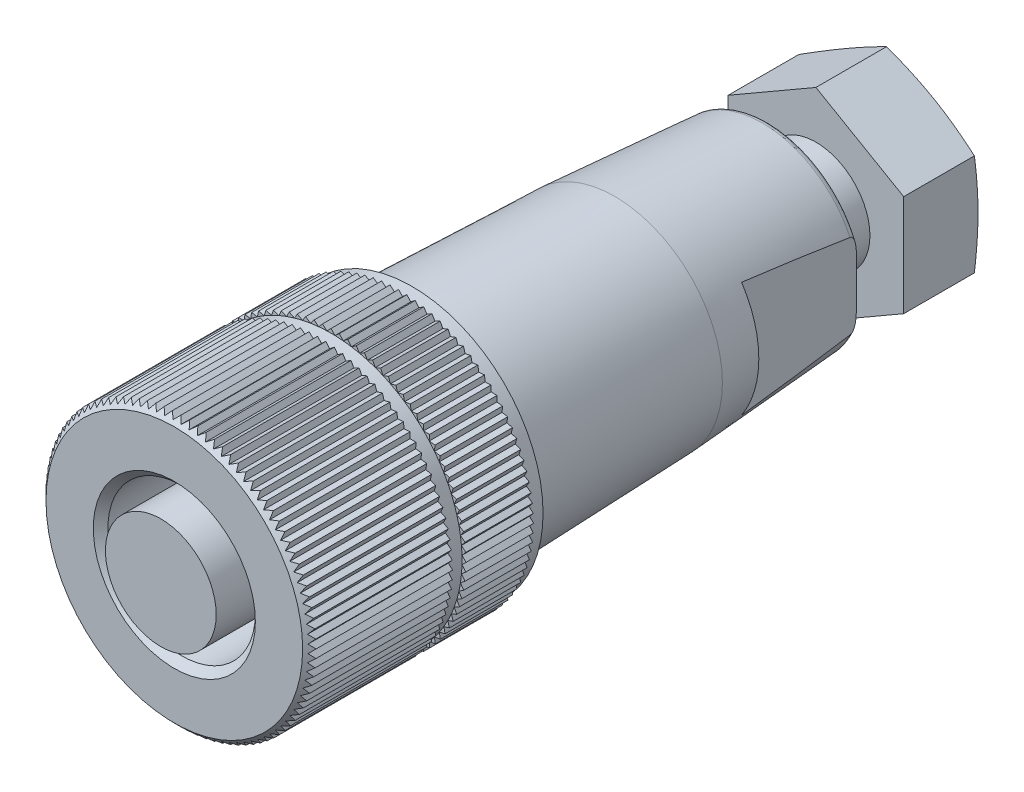
SolidWorks part; units mm, degrees
ref_plane "Ebene vorne" through (0, 0, 0) normal (0, 0, 1) x (1, 0, 0)
ref_plane "Ebene oben" through (0, 0, 0) normal (0, 1, 0) x (1, 0, 0)
ref_plane "Ebene rechts" through (0, 0, 0) normal (1, 0, 0) x (0, 0, -1)
ref_plane "Ebene1" through (0, 0, -26) normal (0, 0, 1) x (1, 0, 0)
sketch "Skizze1" plane through (0, 0, 0) normal (1, 0, 0) x (0, 0, -1)
  line L0 (0, 0) -> (0, 4.1)
  line L1 (0, 4.1) -> (1, 4.1)
  line L2 (1, 4.1) -> (1, 9.5)
  line L3 (1, 9.5) -> (1.5, 10)
  line L4 (1.5, 10) -> (11.6, 10)
  line L5 (11.6, 10) -> (11.6, 9.7)
  line L6 (11.6, 9.7) -> (12.6, 9.7)
  line L7 (12.6, 9.7) -> (12.6, 10)
  line L8 (12.6, 10) -> (17.6, 10)
  line L9 (17.6, 10) -> (17.6, 9.7)
  line L10 (17.6, 9.7) -> (18.6, 9.7)
  line L11 (18.6, 9.7) -> (18.6, 8.5)
  line L12 (18.6, 8.5) -> (33.6, 7.9762)
  line L13 (33.6, 7.9762) -> (44.5349, 7.2115)
  line L14 (45, 6.7128) -> (45, 4)
  line L15 (45, 4) -> (48.5, 4)
  line L16 (48.5, 4) -> (48.5, 7.8)
  line L17 (48.5, 7.8) -> (53.6517, 7.8)
  line L18 (53.6517, 7.8) -> (54, 6.5)
  line L19 (54, 6.5) -> (54, 0)
  line L20 (54, 0) -> (0, 0)
  line L21 (54, 0) -> (0, 0) construction
  arc A0 (44.5349, 7.2115) -> (45, 6.7128) centre (44.5, 6.7128) cw
revolve "Rotation1" add sketch "Skizze1" angle 360 about L21 reverse direction yes
cosmetic thread "Gewindedarstellung1" parameters "D1"=3.5, "D2"=6.773
sketch "Skizze2" plane through (0, 0, 0) normal (1, 0, 0) x (0, 0, -1)
  line L0 (1, 4.1) -> (8.2, 4.1)
  line L1 (8.2, 4.1) -> (8.2, 5.4585)
  line L2 (8.2, 5.4585) -> (1.5415, 5.4585)
  line L3 (1.5415, 5.4585) -> (1, 6)
  line L4 (1, 6) -> (1, 4.1)
  line L5 (8.2, 0) -> (1, 0) construction
revolve "Schnitt-Rotation1" cut sketch "Skizze2" angle 360 about L5 reverse direction yes
cosmetic thread "Gewindedarstellung2" parameters "D1"=5.95, "D2"=12
ref_plane "Ebene2" through (0, 0, -1) normal (0, 0, 1) x (1, 0, 0)
sketch "Skizze3" plane through (0, 0, -1) normal (0, 0, 1) x (1, 0, 0)
  line L0 (-16.1661, -16.1837) -> (13.5761, -16.1837)
  line L1 (13.5761, -16.1837) -> (13.5761, 13.5983)
  line L2 (13.5761, 13.5983) -> (-16.1661, 13.5983)
  line L3 (-16.1661, 13.5983) -> (-16.1661, -16.1837)
  line L4 (-10, -0.0054) -> (-9.695, -0.3101)
  line L5 (-9.695, -0.3101) -> (-9.9799, -0.6335)
  line L6 (-9.9799, -0.6335) -> (-9.6564, -0.9184)
  line L7 (-9.6564, -0.9184) -> (-9.9204, -1.2592)
  line L8 (-9.9204, -1.2592) -> (-9.5797, -1.5231)
  line L9 (-9.5797, -1.5231) -> (-9.8217, -1.8798)
  line L10 (-9.8217, -1.8798) -> (-9.4651, -2.1219)
  line L11 (-9.4651, -2.1219) -> (-9.6843, -2.493)
  line L12 (-9.6843, -2.493) -> (-9.3131, -2.7122)
  line L13 (-9.3131, -2.7122) -> (-9.5085, -3.0964)
  line L14 (-9.5085, -3.0964) -> (-9.1244, -3.2918)
  line L15 (-9.1244, -3.2918) -> (-9.2953, -3.6875)
  line L16 (-9.2953, -3.6875) -> (-8.8996, -3.8584)
  line L17 (-8.8996, -3.8584) -> (-9.0453, -4.2641)
  line L18 (-9.0453, -4.2641) -> (-8.6397, -4.4098)
  line L19 (-8.6397, -4.4098) -> (-8.7596, -4.8238)
  line L20 (-8.7596, -4.8238) -> (-8.3456, -4.9438)
  line L21 (-8.3456, -4.9438) -> (-8.4393, -5.3645)
  line L22 (-8.4393, -5.3645) -> (-8.0186, -5.4582)
  line L23 (-8.0186, -5.4582) -> (-8.0857, -5.884)
  line L24 (-8.0857, -5.884) -> (-7.6599, -5.9511)
  line L25 (-7.6599, -5.9511) -> (-7.7001, -6.3803)
  line L26 (-7.7001, -6.3803) -> (-7.271, -6.4205)
  line L27 (-7.271, -6.4205) -> (-7.2842, -6.8513)
  line L28 (-7.2842, -6.8513) -> (-6.8533, -6.8645)
  line L29 (-6.8533, -6.8645) -> (-6.8395, -7.2953)
  line L30 (-6.8395, -7.2953) -> (-6.4086, -7.2814)
  line L31 (-6.4086, -7.2814) -> (-6.3677, -7.7105)
  line L32 (-6.3677, -7.7105) -> (-5.9386, -7.6696)
  line L33 (-5.9386, -7.6696) -> (-5.8708, -8.0953)
  line L34 (-5.8708, -8.0953) -> (-5.4451, -8.0275)
  line L35 (-5.4451, -8.0275) -> (-5.3507, -8.448)
  line L36 (-5.3507, -8.448) -> (-4.9302, -8.3536)
  line L37 (-4.9302, -8.3536) -> (-4.8095, -8.7675)
  line L38 (-4.8095, -8.7675) -> (-4.3957, -8.6468)
  line L39 (-4.3957, -8.6468) -> (-4.2493, -9.0522)
  line L40 (-4.2493, -9.0522) -> (-3.8439, -8.9059)
  line L41 (-3.8439, -8.9059) -> (-3.6724, -9.3013)
  line L42 (-3.6724, -9.3013) -> (-3.2769, -9.1297)
  line L43 (-3.2769, -9.1297) -> (-3.0809, -9.5136)
  line L44 (-3.0809, -9.5136) -> (-2.697, -9.3175)
  line L45 (-2.697, -9.3175) -> (-2.4772, -9.6883)
  line L46 (-2.4772, -9.6883) -> (-2.1064, -9.4685)
  line L47 (-2.1064, -9.4685) -> (-1.8638, -9.8248)
  line L48 (-1.8638, -9.8248) -> (-1.5075, -9.5821)
  line L49 (-1.5075, -9.5821) -> (-1.243, -9.9224)
  line L50 (-1.243, -9.9224) -> (-0.9027, -9.6579)
  line L51 (-0.9027, -9.6579) -> (-0.6173, -9.9809)
  line L52 (-0.6173, -9.9809) -> (-0.2997, -9.7003)
  line L53 (-0.2997, -9.7003) -> (0, -10)
  line L54 (0, -10) -> (0.3048, -9.6952)
  line L55 (0.3048, -9.6952) -> (0.6281, -9.9803)
  line L56 (0.6281, -9.9803) -> (0.9132, -9.6569)
  line L57 (0.9132, -9.6569) -> (1.2538, -9.9211)
  line L58 (1.2538, -9.9211) -> (1.5179, -9.5805)
  line L59 (1.5179, -9.5805) -> (1.8745, -9.8228)
  line L60 (1.8745, -9.8228) -> (2.1167, -9.4662)
  line L61 (2.1167, -9.4662) -> (2.4877, -9.6856)
  line L62 (2.4877, -9.6856) -> (2.7071, -9.3146)
  line L63 (2.7071, -9.3146) -> (3.0912, -9.5102)
  line L64 (3.0912, -9.5102) -> (3.2868, -9.1262)
  line L65 (3.2868, -9.1262) -> (3.6825, -9.2973)
  line L66 (3.6825, -9.2973) -> (3.8536, -8.9017)
  line L67 (3.8536, -8.9017) -> (4.2592, -9.0476)
  line L68 (4.2592, -9.0476) -> (4.4051, -8.642)
  line L69 (4.4051, -8.642) -> (4.8191, -8.7622)
  line L70 (4.8191, -8.7622) -> (4.9392, -8.3483)
  line L71 (4.9392, -8.3483) -> (5.3599, -8.4422)
  line L72 (5.3599, -8.4422) -> (5.4539, -8.0216)
  line L73 (5.4539, -8.0216) -> (5.8796, -8.0889)
  line L74 (5.8796, -8.0889) -> (5.9469, -7.6631)
  line L75 (5.9469, -7.6631) -> (6.3761, -7.7036)
  line L76 (6.3761, -7.7036) -> (6.4165, -7.2745)
  line L77 (6.4165, -7.2745) -> (6.8474, -7.2879)
  line L78 (6.8474, -7.2879) -> (6.8608, -6.8571)
  line L79 (6.8608, -6.8571) -> (7.2916, -6.8434)
  line L80 (7.2916, -6.8434) -> (7.278, -6.4126)
  line L81 (7.278, -6.4126) -> (7.7071, -6.3719)
  line L82 (7.7071, -6.3719) -> (7.6664, -5.9428)
  line L83 (7.6664, -5.9428) -> (8.0921, -5.8752)
  line L84 (8.0921, -5.8752) -> (8.0245, -5.4495)
  line L85 (8.0245, -5.4495) -> (8.4451, -5.3553)
  line L86 (8.4451, -5.3553) -> (8.351, -4.9347)
  line L87 (8.351, -4.9347) -> (8.7648, -4.8143)
  line L88 (8.7648, -4.8143) -> (8.6444, -4.4004)
  line L89 (8.6444, -4.4004) -> (9.0499, -4.2543)
  line L90 (9.0499, -4.2543) -> (8.9038, -3.8488)
  line L91 (8.9038, -3.8488) -> (9.2993, -3.6774)
  line L92 (9.2993, -3.6774) -> (9.1279, -3.2819)
  line L93 (9.1279, -3.2819) -> (9.5119, -3.086)
  line L94 (9.5119, -3.086) -> (9.3161, -2.7021)
  line L95 (9.3161, -2.7021) -> (9.687, -2.4825)
  line L96 (9.687, -2.4825) -> (9.4674, -2.1116)
  line L97 (9.4674, -2.1116) -> (9.8238, -1.8691)
  line L98 (9.8238, -1.8691) -> (9.5813, -1.5127)
  line L99 (9.5813, -1.5127) -> (9.9218, -1.2484)
  line L100 (9.9218, -1.2484) -> (9.6574, -0.9079)
  line L101 (9.6574, -0.9079) -> (9.9806, -0.6227)
  line L102 (9.9806, -0.6227) -> (9.6954, -0.2995)
  line L103 (9.6954, -0.2995) -> (10, 0.0054)
  line L104 (10, 0.0054) -> (9.695, 0.3101)
  line L105 (9.695, 0.3101) -> (9.9799, 0.6335)
  line L106 (9.9799, 0.6335) -> (9.6564, 0.9184)
  line L107 (9.6564, 0.9184) -> (9.9204, 1.2592)
  line L108 (9.9204, 1.2592) -> (9.5797, 1.5231)
  line L109 (9.5797, 1.5231) -> (9.8217, 1.8798)
  line L110 (9.8217, 1.8798) -> (9.4651, 2.1219)
  line L111 (9.4651, 2.1219) -> (9.6843, 2.493)
  line L112 (9.6843, 2.493) -> (9.3131, 2.7122)
  line L113 (9.3131, 2.7122) -> (9.5085, 3.0964)
  line L114 (9.5085, 3.0964) -> (9.1244, 3.2918)
  line L115 (9.1244, 3.2918) -> (9.2953, 3.6875)
  line L116 (9.2953, 3.6875) -> (8.8996, 3.8584)
  line L117 (8.8996, 3.8584) -> (9.0453, 4.2641)
  line L118 (9.0453, 4.2641) -> (8.6397, 4.4098)
  line L119 (8.6397, 4.4098) -> (8.7596, 4.8238)
  line L120 (8.7596, 4.8238) -> (8.3456, 4.9438)
  line L121 (8.3456, 4.9438) -> (8.4393, 5.3645)
  line L122 (8.4393, 5.3645) -> (8.0186, 5.4582)
  line L123 (8.0186, 5.4582) -> (8.0857, 5.884)
  line L124 (8.0857, 5.884) -> (7.6599, 5.9511)
  line L125 (7.6599, 5.9511) -> (7.7001, 6.3803)
  line L126 (7.7001, 6.3803) -> (7.271, 6.4205)
  line L127 (7.271, 6.4205) -> (7.2842, 6.8513)
  line L128 (7.2842, 6.8513) -> (6.8533, 6.8645)
  line L129 (6.8533, 6.8645) -> (6.8395, 7.2953)
  line L130 (6.8395, 7.2953) -> (6.4086, 7.2814)
  line L131 (6.4086, 7.2814) -> (6.3677, 7.7105)
  line L132 (6.3677, 7.7105) -> (5.9386, 7.6696)
  line L133 (5.9386, 7.6696) -> (5.8708, 8.0953)
  line L134 (5.8708, 8.0953) -> (5.4451, 8.0275)
  line L135 (5.4451, 8.0275) -> (5.3507, 8.448)
  line L136 (5.3507, 8.448) -> (4.9302, 8.3536)
  line L137 (4.9302, 8.3536) -> (4.8095, 8.7675)
  line L138 (4.8095, 8.7675) -> (4.3957, 8.6468)
  line L139 (4.3957, 8.6468) -> (4.2493, 9.0522)
  line L140 (4.2493, 9.0522) -> (3.8439, 8.9059)
  line L141 (3.8439, 8.9059) -> (3.6724, 9.3013)
  line L142 (3.6724, 9.3013) -> (3.2769, 9.1297)
  line L143 (3.2769, 9.1297) -> (3.0809, 9.5136)
  line L144 (3.0809, 9.5136) -> (2.697, 9.3175)
  line L145 (2.697, 9.3175) -> (2.4772, 9.6883)
  line L146 (2.4772, 9.6883) -> (2.1064, 9.4685)
  line L147 (2.1064, 9.4685) -> (1.8638, 9.8248)
  line L148 (1.8638, 9.8248) -> (1.5075, 9.5821)
  line L149 (1.5075, 9.5821) -> (1.243, 9.9224)
  line L150 (1.243, 9.9224) -> (0.9027, 9.6579)
  line L151 (0.9027, 9.6579) -> (0.6173, 9.9809)
  line L152 (0.6173, 9.9809) -> (0.2997, 9.7003)
  line L153 (0.2997, 9.7003) -> (0, 10)
  line L154 (0, 10) -> (-0.3048, 9.6952)
  line L155 (-0.3048, 9.6952) -> (-0.6281, 9.9803)
  line L156 (-0.6281, 9.9803) -> (-0.9132, 9.6569)
  line L157 (-0.9132, 9.6569) -> (-1.2538, 9.9211)
  line L158 (-1.2538, 9.9211) -> (-1.5179, 9.5805)
  line L159 (-1.5179, 9.5805) -> (-1.8745, 9.8228)
  line L160 (-1.8745, 9.8228) -> (-2.1167, 9.4662)
  line L161 (-2.1167, 9.4662) -> (-2.4877, 9.6856)
  line L162 (-2.4877, 9.6856) -> (-2.7071, 9.3146)
  line L163 (-2.7071, 9.3146) -> (-3.0912, 9.5102)
  line L164 (-3.0912, 9.5102) -> (-3.2868, 9.1262)
  line L165 (-3.2868, 9.1262) -> (-3.6825, 9.2973)
  line L166 (-3.6825, 9.2973) -> (-3.8536, 8.9017)
  line L167 (-3.8536, 8.9017) -> (-4.2592, 9.0476)
  line L168 (-4.2592, 9.0476) -> (-4.4051, 8.642)
  line L169 (-4.4051, 8.642) -> (-4.8191, 8.7622)
  line L170 (-4.8191, 8.7622) -> (-4.9392, 8.3483)
  line L171 (-4.9392, 8.3483) -> (-5.3599, 8.4422)
  line L172 (-5.3599, 8.4422) -> (-5.4539, 8.0216)
  line L173 (-5.4539, 8.0216) -> (-5.8796, 8.0889)
  line L174 (-5.8796, 8.0889) -> (-5.9469, 7.6631)
  line L175 (-5.9469, 7.6631) -> (-6.3761, 7.7036)
  line L176 (-6.3761, 7.7036) -> (-6.4165, 7.2745)
  line L177 (-6.4165, 7.2745) -> (-6.8474, 7.2879)
  line L178 (-6.8474, 7.2879) -> (-6.8608, 6.8571)
  line L179 (-6.8608, 6.8571) -> (-7.2916, 6.8434)
  line L180 (-7.2916, 6.8434) -> (-7.278, 6.4126)
  line L181 (-7.278, 6.4126) -> (-7.7071, 6.3719)
  line L182 (-7.7071, 6.3719) -> (-7.6664, 5.9428)
  line L183 (-7.6664, 5.9428) -> (-8.0921, 5.8752)
  line L184 (-8.0921, 5.8752) -> (-8.0245, 5.4495)
  line L185 (-8.0245, 5.4495) -> (-8.4451, 5.3553)
  line L186 (-8.4451, 5.3553) -> (-8.351, 4.9347)
  line L187 (-8.351, 4.9347) -> (-8.7648, 4.8143)
  line L188 (-8.7648, 4.8143) -> (-8.6444, 4.4004)
  line L189 (-8.6444, 4.4004) -> (-9.0499, 4.2543)
  line L190 (-9.0499, 4.2543) -> (-8.9038, 3.8488)
  line L191 (-8.9038, 3.8488) -> (-9.2993, 3.6774)
  line L192 (-9.2993, 3.6774) -> (-9.1279, 3.2819)
  line L193 (-9.1279, 3.2819) -> (-9.5119, 3.086)
  line L194 (-9.5119, 3.086) -> (-9.3161, 2.7021)
  line L195 (-9.3161, 2.7021) -> (-9.687, 2.4825)
  line L196 (-9.687, 2.4825) -> (-9.4674, 2.1116)
  line L197 (-9.4674, 2.1116) -> (-9.8238, 1.8691)
  line L198 (-9.8238, 1.8691) -> (-9.5813, 1.5127)
  line L199 (-9.5813, 1.5127) -> (-9.9218, 1.2484)
  line L200 (-9.9218, 1.2484) -> (-9.6574, 0.9079)
  line L201 (-9.6574, 0.9079) -> (-9.9806, 0.6227)
  line L202 (-9.9806, 0.6227) -> (-9.6954, 0.2995)
  line L203 (-9.6954, 0.2995) -> (-10, -0.0054)
extrude "Schnitt-Linear austragen1" cut sketch "Skizze3" against normal blind 16.6
ref_plane "Ebene3" through (0, 0, -48.5) normal (0, 0, 1) x (1, 0, 0)
sketch "Skizze4" plane through (0, 0, -48.5) normal (0, 0, 1) x (1, 0, 0)
  line L0 (-17, -17) -> (17, -17)
  line L1 (17, -17) -> (17, 17)
  line L2 (17, 17) -> (-17, 17)
  line L3 (-17, 17) -> (-17, -17)
  line L4 (-6.5, -3.7528) -> (0, -7.5056)
  line L5 (0, -7.5056) -> (6.5, -3.7528)
  line L6 (6.5, -3.7528) -> (6.5, 3.7528)
  line L7 (6.5, 3.7528) -> (0, 7.5056)
  line L8 (0, 7.5056) -> (-6.5, 3.7528)
  line L9 (-6.5, 3.7528) -> (-6.5, -3.7528)
extrude "Schnitt-Linear austragen2" cut sketch "Skizze4" against normal blind 6
sketch "Skizze5" plane through (0, 0, -48.5) normal (0, 0, 1) x (1, 0, 0)
  line L0 (-20, -30) -> (20, -30)
  line L1 (20, -30) -> (20, 30)
  line L2 (20, 30) -> (-20, 30)
  line L3 (-20, 30) -> (-20, -30)
  line L4 (-6.5, -20) -> (6.5, -20)
  line L5 (6.5, -20) -> (6.5, 20)
  line L6 (6.5, 20) -> (-6.5, 20)
  line L7 (-6.5, 20) -> (-6.5, -20)
extrude "Schnitt-Linear austragen3" cut sketch "Skizze5" along normal blind 12
ref_plane "Ebene4" through (0, 0, -54) normal (0, 0, 1) x (1, 0, 0)
sketch "Skizze6" plane through (0, 0, -54) normal (0, 0, 1) x (1, 0, 0)
  circle A0 centre (0, 0) radius 3
extrude "Schnitt-Linear austragen4" cut sketch "Skizze6" along normal blind 5
